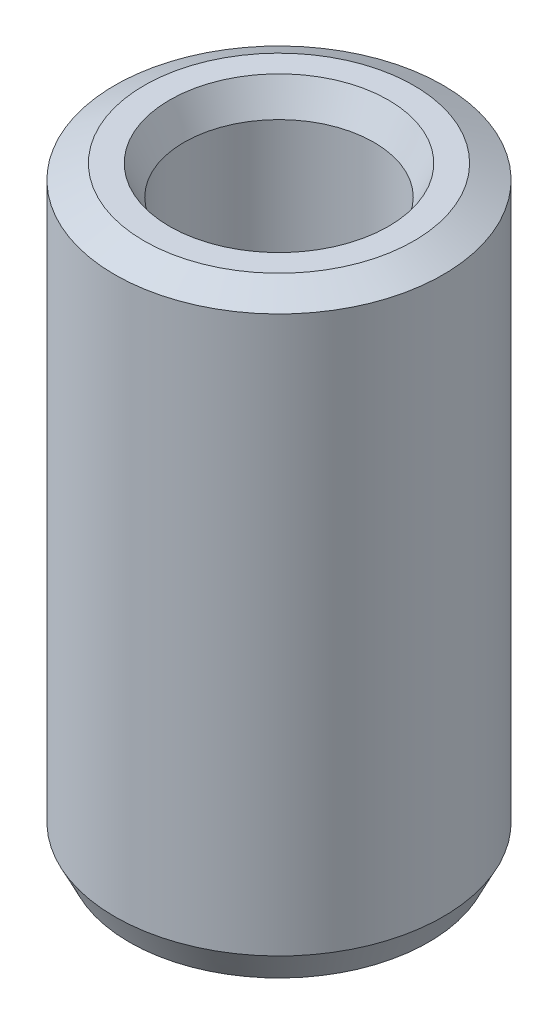
SolidWorks part; units mm, degrees
ref_plane "Front Plane" through (0, 0, 0) normal (0, 0, 1) x (1, 0, 0)
ref_plane "Top Plane" through (0, 0, 0) normal (0, 1, 0) x (1, 0, 0)
ref_plane "Right Plane" through (0, 0, 0) normal (1, 0, 0) x (0, 0, -1)
sketch "Sketch1" plane through (0, 0, 0) normal (0, 1, 0) x (1, 0, 0)
  circle A0 centre (0, 0) radius 45
  dimension "SLEEVE_OD" = 90
extrude "Boss-Extrude1" add sketch "Sketch1" along normal blind 164.4686
sketch "Sketch2" plane through (0, 0, 0) normal (0, 1, 0) x (1, 0, 0)
  circle A0 centre (0, 0) radius 26.0327
  dimension "BORE_D" = 52.0653
extrude "Cut-Extrude1" cut sketch "Sketch2" along normal through all
chamfer "Chamfer1" distance 3.9835 angle 63.654 4 edges at (0, 164.4686, 26.0327) (0, 0, 26.0327) (0, 0, 45) (0, 164.4686, 45) first distance on face at (0, 164.4686, 26.0327) first distance on face at (0, 0, 26.0327) first distance on face at (0, 164.4686, 45)
